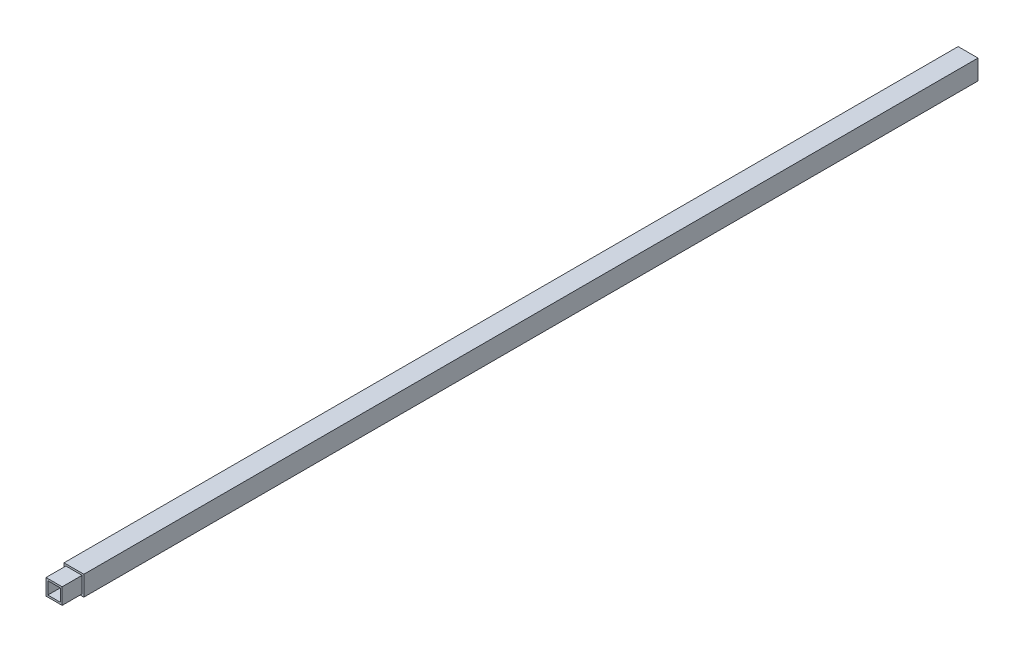
SolidWorks part; units mm, degrees
ref_plane "Plane1" through (0, 0, 0) normal (0, 0, 1) x (1, 0, 0)
ref_plane "Plane2" through (0, 0, 0) normal (0, 1, 0) x (1, 0, 0)
ref_plane "Plane3" through (0, 0, 0) normal (1, 0, 0) x (0, 0, -1)
sketch "Sketch1" plane through (0, 0, 0) normal (0, 0, 1) x (1, 0, 0)
  line L0 (4.7625, 4.7625) -> (4.7625, 46.0375)
  line L1 (46.0375, 46.0375) -> (4.7625, 46.0375)
  line L2 (46.0375, 46.0375) -> (46.0375, 4.7625)
  line L3 (4.7625, 4.7625) -> (46.0375, 4.7625)
  line L4 (0, 0) -> (50.8, 0)
  line L5 (0, 0) -> (0, 50.8)
  line L6 (50.8, 50.8) -> (0, 50.8)
  line L7 (50.8, 50.8) -> (50.8, 0)
  line L8 (9.525, 9.525) -> (9.525, 41.275)
  line L9 (41.275, 41.275) -> (9.525, 41.275)
  line L10 (41.275, 41.275) -> (41.275, 9.525)
  line L11 (9.525, 9.525) -> (41.275, 9.525)
  dimension "Thickness" = 4.7625
  dimension "D1" = 4.7625
extrude "BaseTube" add sketch "Sketch1" along normal mid plane 2286 contours L7 L6 L5 L4 L3 L0 L1 L2 region at (0.7184, 25.4, 0)
extrude "Boss-Extrude2" add sketch "Sketch1<3>" along normal mid plane 101.6 from vertex contours L0 L3 L2 L1 L11 L8 L9 L10 region at (5.3462, 25.4, 0) starting at point (46.0375, 46.0375, 1143)
sketch "Sketch1<3>" plane through (0, 0, 0) normal (0, 0, 1) x (1, 0, 0) same geometry as "Sketch1"
